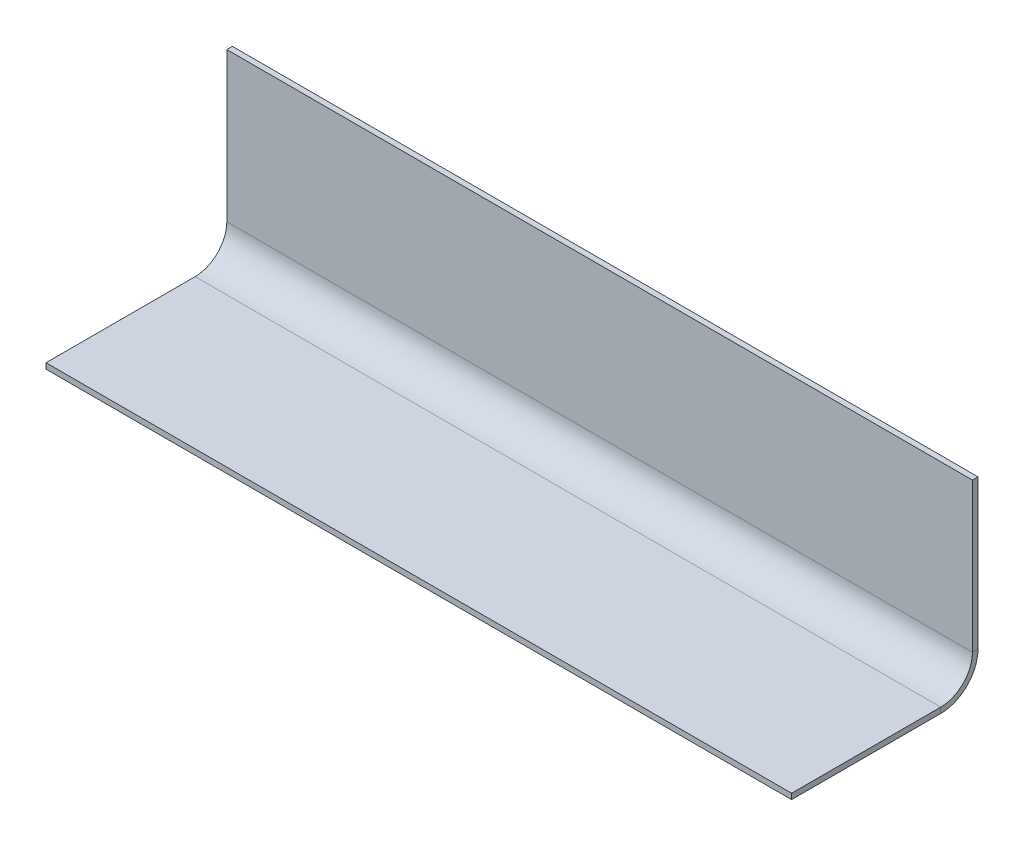
SolidWorks part; units mm, degrees
note: The reader was unsure of these and kept them because the rebuilt part matched: thickness of "基体-法兰1", "边线-法兰1", "钣金6", "钣金7"; flange length of "边线-法兰1".
ref_plane "前视基准面" through (0, 0, 0) normal (0, 0, 1) x (1, 0, 0)
ref_plane "上视基准面" through (0, 0, 0) normal (0, 1, 0) x (1, 0, 0)
ref_plane "右视基准面" through (0, 0, 0) normal (1, 0, 0) x (0, 0, -1)
sketch "草图2" plane through (0, 0, 0) normal (0, 0, 1) x (1, 0, 0)
  line L1 (-200, 50) -> (200, 50)
  line L2 (-200, 50) -> (-200, -50)
  line L3 (-200, -50) -> (200, -50)
  line L4 (200, 50) -> (200, -50)
  line L5 (-200, 50) -> (200, -50) construction
  line L6 (-200, -50) -> (200, 50) construction
  point P0 (0, 0)
  dimension "D1" = 400
  dimension "D2" = 100
base flange "基体-法兰1" sketch "草图2" thickness 3 reverse thickness direction no parameters "D1"=0.7366
edge flange "边线-法兰1" sketch "草图22" flange angle 90 flange length 100 flange position material inside bend radius 17 thickness 3 relief rectangular parameters "D6"=10
bend "边线折弯4" bend radius 17 bend angle 90 parameters "D5"=1
sketch "草图22" plane through (0, -50, 0) normal (0, 1, 0) x (-1, 0, 0)
  line L0 (-200, -3) -> (200, -3) construction
  line L1 (200, 0) -> (-200, 0) construction
  line L2 (-200, 0) -> (-200, 97)
  line L3 (-200, 97) -> (200, 97)
  line L4 (200, 97) -> (200, 0)
  line L5 (200, 0) -> (-200, 0)
  dimension "D1" = 100
sketch "折弯-线1" plane through (0, 0, 0) normal (0, 1, 0) x (1, 0, 0)
sketch "边界框1" plane through (0, 0, 0) normal (0, 1, 0) x (1, 0, 0)
sheet metal parameters "钣金6" thickness 3 parameters "D1"=0.7366, "D7"=1.5
flat pattern "平板型式6" [suppressed]
sketch "折弯-线2" plane through (0, 0, 0) normal (0, 1, 0) x (1, 0, 0)
sketch "边界框2" [suppressed] plane through (0, 0, 0) normal (0, 1, 0) x (1, 0, 0)
sheet metal parameters "钣金7" thickness 3 parameters "D1"=0.7366, "D7"=1.5
flat pattern "平板型式6" [suppressed]
sketch "折弯-线2" plane through (0, 0, 0) normal (0, 1, 0) x (1, 0, 0)
sketch "边界框2" [suppressed] plane through (0, 0, 0) normal (0, 1, 0) x (1, 0, 0)
bend of the flat pattern "展开-<边线折弯4>1"
